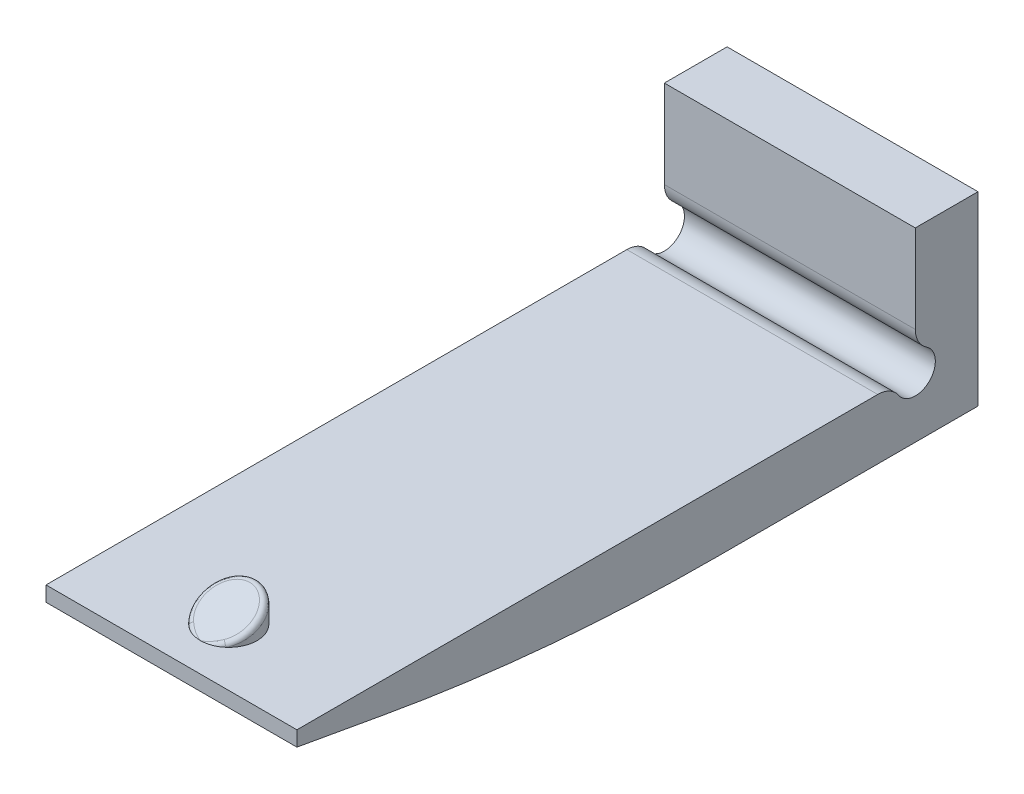
SolidWorks part; units mm, degrees
ref_plane "Front Plane" through (0, 0, 0) normal (0, 0, 1) x (1, 0, 0)
ref_plane "Top Plane" through (0, 0, 0) normal (0, 1, 0) x (1, 0, 0)
ref_plane "Right Plane" through (0, 0, 0) normal (1, 0, 0) x (0, 0, -1)
sketch "Sketch1" plane through (0, 0, 0) normal (1, 0, 0) x (0, 0, -1)
  line L0 (-38.735, 0) -> (0, 0)
  line L1 (0, 0) -> (0, 9.398)
  line L2 (0, 9.398) -> (-3.175, 9.398)
  line L3 (-3.175, 9.398) -> (-3.175, 3.048)
  line L4 (-3.175, 3.048) -> (-38.735, 3.048)
  line L5 (-38.735, 3.048) -> (-38.735, 0)
  line L6 (-34.4746, 3.048) -> (-34.4746, 2.286)
  line L7 (-38.735, 4.5466) -> (-38.735, 1.4986)
  line L8 (-38.735, 1.4986) -> (-30.0722, 1.4986)
  line L9 (-30.0722, 1.4986) -> (-30.0722, 4.5466)
  line L10 (-30.0722, 4.5466) -> (-38.735, 4.5466)
  line L11 (-31.5722, 3.048) -> (-31.5722, 4.5466) construction
  line L12 (-30.0722, 4.5466) -> (-30.0722, 3.048) construction
  line L13 (-38.735, 3.048) -> (-30.0722, 1.4986)
  circle A1 centre (-3.175, 3.048) radius 1.016
  arc A2 (-13.1817, 0) -> (-30.0722, 1.4986) centre (-13.1817, 95.9346) cw
  dimension "D1" = 3.048
  dimension "D5" = 2.032
  dimension "D2" = 35.56
  dimension "D3" = 3.175
  dimension "D4" = 6.35
  dimension "D6" = 0.762
  dimension "D7" = 1.4986
  dimension "D8" = 3.048
  dimension "D9" = 28.3972
  dimension "D10" = 1.5
extrude "Boss-Extrude1" add sketch "Sketch1" along normal blind 12.7 contours L5 L13 L9 L4 | A2 L1 L2 L3 A1 L4 L9 region at (0, 2.5185, 11.7389) region at (0, 2.4478, 32.0234)
sketch "Sketch2" plane through (0, 3.048, 0) normal (0, 1, 0) x (1, 0, 0)
  line L1 (12.7, -3.175) -> (0, -3.175) construction
  line L4 (12.7, -38.735) -> (0, -38.735) construction
  circle A0 centre (6.35, -31.5722) radius 1.4351
  point P5 (6.35, -38.735)
  dimension "D1" = 2.8702
  dimension "D2" = 28.3972
extrude "Boss-Extrude2" add sketch "Sketch2" along normal blind 2.9972
sketch "Sketch3" plane through (12.7, 0, 0) normal (1, 0, 0) x (0, 0, -1)
  line L0 (-33.0073, 3.048) -> (-30.1371, 4.5466)
  line L1 (-30.1371, 3.048) -> (-30.1371, 6.0452) construction
  line L2 (-30.1371, 4.5466) -> (-30.1371, 6.0452)
  line L3 (-30.1371, 6.0452) -> (-33.0073, 6.0452)
  line L4 (-33.0073, 6.0452) -> (-33.0073, 3.048)
extrude "Cut-Extrude1" cut sketch "Sketch3" against normal through all contours L4 L0 L2 L3
fillet "Fillet1" radius 0.254 1 edges at (6.35, 3.048, 33.0073)
fillet "Fillet2" radius 1.27 2 edges at (6.35, 4.064, 3.175) (6.35, 3.048, 4.191)
